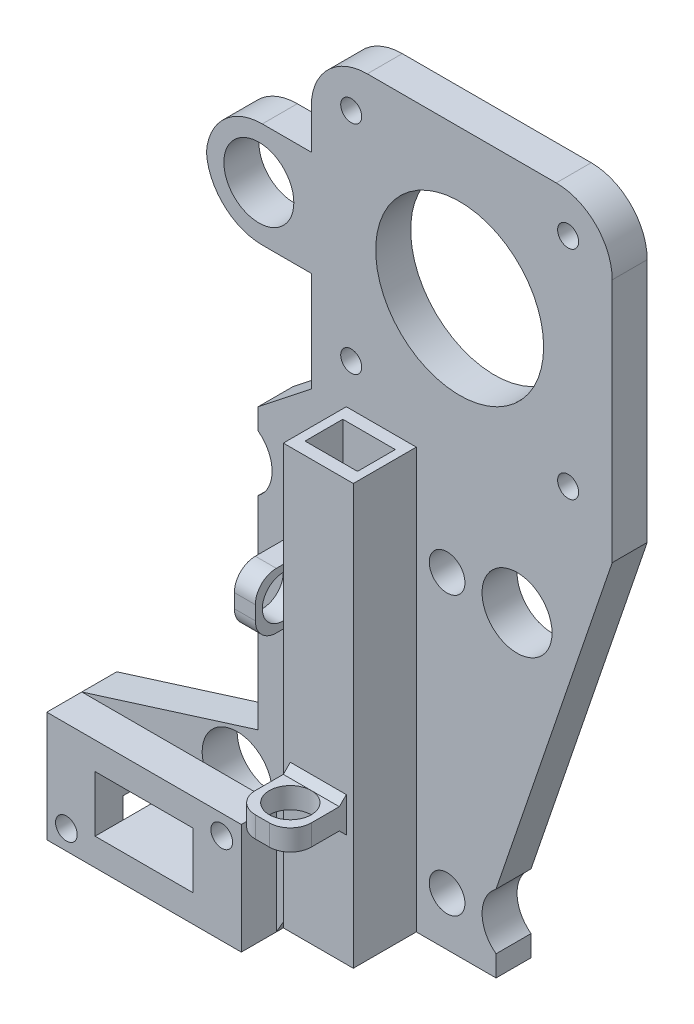
SolidWorks part; units mm, degrees
ref_plane "Front Plane" through (0, 0, 0) normal (0, 0, 1) x (1, 0, 0)
ref_plane "Top Plane" through (0, 0, 0) normal (0, 1, 0) x (1, 0, 0)
ref_plane "Right Plane" through (0, 0, 0) normal (1, 0, 0) x (0, 0, -1)
sketch "Sketch1" plane through (0, 0, 0) normal (0, 0, 1) x (1, 0, 0)
  line L0 (7, 46.7) -> (27, 46.7) construction
  line L1 (0, 0) -> (34, 0)
  line L2 (0, 0) -> (0, 3)
  line L3 (0, 53.7) -> (34, 53.7)
  line L4 (34, 0) -> (34, 3)
  line L5 (27, 46.7) -> (27, 7) construction
  line L6 (27, 7) -> (7, 7) construction
  line L7 (7, 7) -> (7, 46.7) construction
  line L8 (-3, 46.7) -> (37, 46.7) construction
  line L9 (37, 46.7) -> (37, 7) construction
  line L10 (37, 7) -> (-3, 7) construction
  line L11 (-3, 7) -> (-3, 46.7) construction
  line L12 (0, 50.7) -> (0, 53.7)
  line L13 (34, 50.7) -> (34, 53.7)
  line L14 (34, 11) -> (34, 42.7)
  line L15 (0, 11) -> (0, 42.7)
  circle A0 centre (7, 46.7) radius 2.55
  circle A1 centre (27, 46.7) radius 2.55
  circle A2 centre (7, 7) radius 2.55
  circle A3 centre (27, 7) radius 2.55
  arc A4 (0, 42.7) -> (0, 50.7) centre (-3, 46.7) ccw
  arc A5 (34, 50.7) -> (34, 42.7) centre (37, 46.7) ccw
  arc A6 (34, 11) -> (34, 3) centre (37, 7) ccw
  arc A7 (0, 3) -> (0, 11) centre (-3, 7) ccw
  dimension "D3" = 5.1
  dimension "D10" = 10
  dimension "D1" = 20
  dimension "D2" = 39.7
  dimension "D4" = 7
  dimension "D5" = 7
  dimension "D6" = 7
  dimension "D7" = 7
  dimension "D8" = 10
  dimension "D9" = 10
extrude "Boss-Extrude1" add sketch "Sketch1" along normal blind 5
sketch "Sketch2" plane through (0, 0, 5) normal (0, 0, 1) x (1, 0, 0)
  line L0 (7, 46.7) -> (27, 46.7) construction
  line L1 (12.6, 60) -> (22.6, 60)
  line L2 (12.6, 60) -> (12.6, 0)
  line L3 (12.6, 0) -> (22.6, 0)
  line L4 (22.6, 60) -> (22.6, 0)
  line L5 (7, 7) -> (27, 7) construction
  line L8 (0, 0) -> (34, 0) construction
  line L9 (0, 42.7) -> (0, 11) construction
  circle A0 centre (7, 7) radius 2.55 construction
  circle A1 centre (27, 7) radius 2.55 construction
  circle A2 centre (27, 46.7) radius 2.55 construction
  circle A3 centre (7, 46.7) radius 2.55 construction
  circle A4 centre (7, 7) radius 2.55
  circle A5 centre (27, 7) radius 2.55
  circle A6 centre (27, 46.7) radius 2.55
  circle A7 centre (7, 46.7) radius 2.55
  dimension "D1" = 10
  dimension "D2" = 12.6
  dimension "D3" = 60
extrude "Boss-Extrude2" add sketch "Sketch2" along normal blind 9 contours L4 L1 L2 L3 | L2 L1 L4 L3 region at (17.6, 30, 5)
sketch "Sketch3" plane through (0, 0, 5) normal (0, 0, 1) x (1, 0, 0)
  line L0 (12.6, 60) -> (12.6, 0) construction
  line L2 (2.6, 5.8) -> (2.6, -10)
  line L3 (2.6, -10) -> (-25.2, -10)
  line L4 (-25.2, 5.8) -> (-25.2, -10)
  line L5 (-25.2, 5.8) -> (2.6, 5.8)
  line L6 (0, 0) -> (12.6, 0) construction
  circle A0 centre (7, 7) radius 4
  dimension "D3" = 8
  dimension "D5" = 10
  dimension "D1" = 27.8
  dimension "D2" = 15.8
  dimension "D4" = 10
extrude "Boss-Extrude3" add sketch "Sketch3" along normal blind 5 contours L5 L4 L3 L2 | L5 L2 L3 L4 region at (-11.3, -2.1, 5)
sketch "Sketch6" plane through (0, 0, 5) normal (0, 0, 1) x (1, 0, 0)
  line L0 (0, 53.7) -> (0, 50.7) construction
  line L5 (7.6, 102.7) -> (50.6, 102.7)
  line L6 (7.6, 102.7) -> (7.6, 59.7)
  line L7 (7.6, 59.7) -> (50.6, 59.7)
  line L8 (50.6, 102.7) -> (50.6, 59.7)
  line L9 (7.6, 59.7) -> (0, 53.7)
  line L10 (0, 53.7) -> (34, 53.7)
  line L11 (34, 53.7) -> (50.6, 59.7)
  circle A0 centre (27, 46.7) radius 2.55 construction
  line M23 (34, 53.7) -> (22.6, 53.7)
  dimension "D3" = 13
  dimension "D1" = 43
  dimension "D2" = 43
  dimension "D4" = 7.6
extrude "Boss-Extrude4" add sketch "Sketch6" against normal through all contours L8 L5 L6 L7 | L11 L7 L9 M23 region at (29.1, 81.2, 5) region at (23.2857, 56.8169, 5)
sketch "Sketch8" plane through (0, 0, 5) normal (0, 0, 1) x (1, 0, 0)
  line L0 (13.3, 97) -> (44.3, 97) construction
  line L1 (44.3, 97) -> (44.3, 66) construction
  line L2 (44.3, 66) -> (13.3, 66) construction
  line L3 (13.3, 66) -> (13.3, 97) construction
  line L4 (7.6, 102.7) -> (7.6, 59.7) construction
  line L5 (7.6, 102.7) -> (50.6, 102.7) construction
  line L6 (28.8, 97) -> (28.8, 66) construction
  line L7 (13.3, 81.5) -> (44.3, 81.5) construction
  circle A0 centre (13.3, 97) radius 1.5
  circle A1 centre (44.3, 97) radius 1.5
  circle A2 centre (13.3, 66) radius 1.5
  circle A3 centre (44.3, 66) radius 1.5
  circle A4 centre (28.8, 81.5) radius 12
  point P18 (28.8, 81.5)
  dimension "D5" = 3
  dimension "D6" = 24
  dimension "D1" = 5.7
  dimension "D2" = 5.7
  dimension "D3" = 31
  dimension "D4" = 31
extrude "Cut-Extrude3" cut sketch "Sketch8" against normal through all
sketch "Sketch9" plane through (0, 0, 5) normal (0, 0, 1) x (1, 0, 0)
  line L0 (50.6, 59.7) -> (34, 11)
  circle A0 centre (37, 46.7) radius 5
  line M18 (34, 11) -> (34, 42.7)
  line M20 (34, 50.7) -> (34, 53.7)
  line M21 (34, 53.7) -> (50.6, 59.7)
  dimension "D1" = 10
extrude "Boss-Extrude5" add sketch "Sketch9" against normal up to surface (5 mm away) contours A0 L0 M18 M21 M20 region at (39.9791, 40.2387, 5) up to face at (45.8, 97, 0)
fillet "Fillet1" radius 8 2 edges at (7.6, 102.7, 2.5) (50.6, 102.7, 2.5)
sketch "Sketch11" plane through (0, 0, 5) normal (0, 0, -1) x (-1, 0, 0)
  line L0 (-2.6, -10) -> (-8.3735, 0)
  line L1 (0, 0) -> (-34, 0) construction
  line L2 (-8.3735, 0) -> (0, 0)
  line L3 (0, 0) -> (0, 3)
  line L4 (-2.6, -10) -> (25.2, -10)
  line L5 (25.2, -10) -> (25.2, 5.8)
  line L8 (-2.6, 0) -> (-2.6, -10) construction
  line L9 (25.2, 5.8) -> (0, 13.7054)
  line L10 (0, 42.7) -> (0, 11) construction
  line L11 (0, 13.7054) -> (0, 11)
  arc A1 (0, 3) -> (0, 11) centre (3, 7) ccw
  arc A2 (0, 11) -> (0, 3) centre (3, 7) ccw construction
  dimension "D2" = 5.5
  dimension "D1" = 30
extrude "Boss-Extrude7" add sketch "Sketch11" along normal up to surface (5 mm away) up to face at (42, 46.7, 0)
sketch "Sketch12" plane through (0, 0, 10) normal (0, 0, 1) x (1, 0, 0)
  line L0 (2.6, -10) -> (-25.2, -10) construction
  line L1 (-25.2, 5.8) -> (-25.2, -10) construction
  line L2 (-25.2, 5.8) -> (2.6, 5.8) construction
  line L3 (2.6, 5.8) -> (2.6, -10) construction
  circle A0 centre (-22.4, -7.2) radius 1.55
  circle A1 centre (-0.2, 3) radius 1.55
  dimension "D1" = 3.1
  dimension "D2" = 2.8
  dimension "D3" = 2.8
  dimension "D4" = 2.8
  dimension "D5" = 2.8
extrude "Cut-Extrude4" cut sketch "Sketch12" against normal up to surface (10 mm away) up to face at (13.9514, 39.8894, 0)
sketch "Sketch13" plane through (0, 0, 5) normal (0, 0, 1) x (1, 0, 0)
  line L0 (7.6, 94.7) -> (7.6, 59.7) construction
  line L1 (7.6, 74) -> (-7.4, 74)
  line L2 (7.6, 74) -> (7.6, 89)
  line L3 (7.6, 89) -> (-7.4, 89)
  line L4 (-7.4, 74) -> (-7.4, 89)
  line L5 (0.1, 89) -> (0.1, 74) construction
  line L6 (-7.4, 81.5) -> (7.6, 81.5) construction
  circle A0 centre (0.1, 81.5) radius 5
  circle A1 centre (28.8, 81.5) radius 12 construction
  circle A2 centre (28.8, 81.5) radius 12
  point P12 (0.1, 81.5)
  line M14 (7.6, 94.7) -> (7.6, 59.7)
  dimension "D3" = 10
  dimension "D1" = 15
  dimension "D2" = 15
extrude "Boss-Extrude8" add sketch "Sketch13" along direction (0, 0, 1) on the side against the normal up to surface (5 mm away) contours L4 L1 L3 A0 M14 region at (0.1, 74.2121, 5) up to face at (-20.85, -7.2, 0)
fillet "Fillet2" radius 8 2 edges at (-7.4, 74, 2.5) (-7.4, 89, 2.5)
sketch "Sketch14" plane through (0, 0, 10) normal (0, 0, 1) x (1, 0, 0)
  line L1 (-18.3, 1.9) -> (-4.3, 1.9)
  line L2 (-18.3, 1.9) -> (-18.3, -6.1)
  line L3 (-18.3, -6.1) -> (-4.3, -6.1)
  line L4 (-4.3, 1.9) -> (-4.3, -6.1)
  line L6 (-11.3, 1.9) -> (-11.3, -6.1) construction
  line L7 (-18.3, -2.1) -> (-4.3, -2.1) construction
  line L8 (-25.2, 5.8) -> (-25.2, -10) construction
  line L9 (2.6, 5.8) -> (2.6, -10) construction
  line L10 (-25.2, 5.8) -> (2.6, 5.8) construction
  line L11 (2.6, -10) -> (-25.2, -10) construction
  dimension "D1" = 14
  dimension "D2" = 8
extrude "Cut-Extrude5" cut sketch "Sketch14" against normal through all
sketch "Sketch15" plane through (0, 0, 0) normal (0, -1, 0) x (1, 0, 0)
  line L0 (12.6, 9.5) -> (22.6, 9.5) construction
  line L1 (12.6, 14) -> (12.6, 5) construction
  line L2 (22.6, 14) -> (22.6, 5) construction
  line L4 (13.9, 12.2) -> (21.4, 12.2)
  line L5 (13.9, 12.2) -> (13.9, 6.8)
  line L6 (13.9, 6.8) -> (21.4, 6.8)
  line L7 (21.4, 12.2) -> (21.4, 6.8)
  dimension "D1" = 5.4
  dimension "D2" = 7.5
  dimension "D3" = 1.3
extrude "Cut-Extrude6" cut sketch "Sketch15" against normal up to surface (60 mm away) up to face at (17.6, 60, 9.5)
ref_plane "Plane1" through (0, 20, 0) normal (0, -1, 0) x (-1, 0, 0)
sketch "Sketch17" plane through (0, 20, 0) normal (0, -1, 0) x (-1, 0, 0)
  line L0 (-12.6, -14) -> (-22.6, -14) construction
  line L1 (-21.6, -14) -> (-13.6, -14)
  line L2 (-21.6, -14) -> (-21.6, -22)
  line L3 (-21.6, -22) -> (-13.6, -22)
  line L4 (-13.6, -14) -> (-13.6, -22)
  line L5 (-17.6, -14) -> (-17.6, -4.5937) construction
  line L6 (-22.6, -14) -> (-22.6, -5) construction
  line L7 (-12.6, -14) -> (-12.6, -5) construction
  line L8 (-21.6, -18) -> (-13.6, -18) construction
  circle A0 centre (-17.6, -18) radius 3
  dimension "D3" = 6
  dimension "D1" = 8
  dimension "D2" = 8
extrude "Boss-Extrude10" add sketch "Sketch17" along normal blind 3
fillet "Fillet4" radius 3 2 edges at (13.6, 18.5, 22) (21.6, 18.5, 22)
chamfer "Chamfer1" distance 1 angle 45 2 edges at (17.6, 17, 14) (17.6, 20, 14)
ref_plane "Plane2" through (7.6, 0, 0) normal (-1, 0, 0) x (0, 0, 1)
sketch "Sketch18" plane through (7.6, 0, 0) normal (-1, 0, 0) x (0, 0, 1)
  line L0 (5, 60) -> (5, 0) construction
  line L1 (5, 40) -> (13, 40)
  line L2 (5, 40) -> (5, 32)
  line L3 (5, 32) -> (13, 32)
  line L4 (13, 40) -> (13, 32)
  line L5 (5, 36) -> (13, 36) construction
  line L6 (9, 32) -> (9, 40) construction
  line L7 (14, 60) -> (5, 60) construction
  circle A0 centre (9, 36) radius 3
  dimension "D3" = 6
  dimension "D1" = 8
  dimension "D2" = 8
  dimension "D4" = 20
extrude "Boss-Extrude11" add sketch "Sketch18" along normal blind 3
fillet "Fillet5" radius 3 2 edges at (6.1, 32, 13) (6.1, 40, 13)
chamfer "Chamfer2" distance 1 angle 45 4 edges at (7.6, 36, 5) (6.1, 32, 5) (4.6, 36, 5) (6.1, 40, 5)
sketch "Sketch19" plane through (0, 0, 0) normal (0, 0, -1) x (-1, 0, 0)
  line L0 (18.3, 1.9) -> (18.3, -6.1) construction
  line L1 (25.2, -10) -> (18.3, -10)
  line L2 (25.2, -10) -> (25.2, -3.1)
  line L3 (25.2, -3.1) -> (18.3, -3.1)
  line L4 (18.3, -10) -> (18.3, -3.1)
extrude "Cut-Extrude7" cut sketch "Sketch19" against normal blind 6
